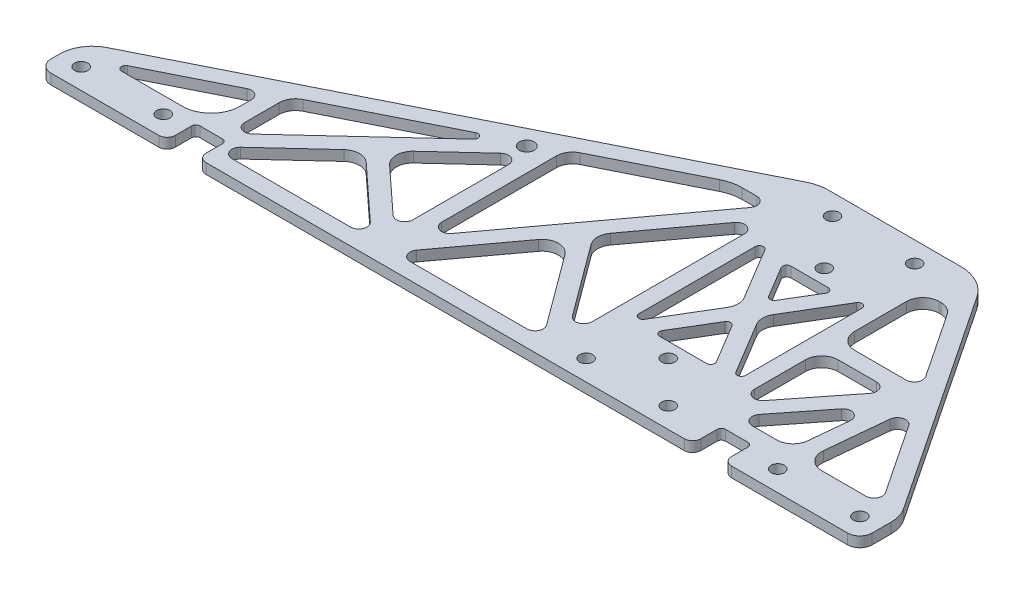
SolidWorks part; units mm, degrees
ref_plane "Front Plane" through (0, 0, 0) normal (0, 0, 1) x (1, 0, 0)
ref_plane "Top Plane" through (0, 0, 0) normal (0, 1, 0) x (1, 0, 0)
ref_plane "Right Plane" through (0, 0, 0) normal (1, 0, 0) x (0, 0, -1)
sketch "Sketch1" plane through (0, 0, 0) normal (0, 1, 0) x (1, 0, 0)
  line L0 (0, 0) -> (254, 0)
  line L2 (203.2, 88.9) -> (152.4, 88.9)
  line L4 (0, 0) -> (0, 12.7)
  line L5 (0, 12.7) -> (152.4, 88.9)
  line L6 (203.2, 88.9) -> (254, 12.7)
  line L7 (254, 12.7) -> (254, 0)
  line L8 (0, 6.35) -> (44.45, 6.35) construction
  line L9 (254, 6.35) -> (222.25, 6.35) construction
  line L10 (139.7, 82.55) -> (207.4333, 82.55) construction
  line L11 (44.45, 0) -> (44.45, 34.925) construction
  line L12 (156.6333, 12.7) -> (154.0933, 7.62)
  line L13 (224.7006, 47.4909) -> (221.314, 12.7) construction
  line L20 (127, 76.2) -> (211.6667, 76.2)
  line L21 (154.0933, 76.2) -> (101.6, 5.08) construction
  line L22 (154.0933, 12.7) -> (154.0933, 7.62)
  line L23 (247.8946, 12.7) -> (194.7333, 12.7)
  line L24 (224.7006, 47.4909) -> (197.2733, 12.7) construction
  line L28 (224.7006, 47.4909) -> (194.7333, 47.4909) construction
  line L31 (5.08, 9.5604) -> (153.5992, 83.82)
  line L32 (200.4813, 83.82) -> (153.5992, 83.82)
  line L33 (200.4813, 83.82) -> (248.92, 11.1619)
  line L34 (248.92, 11.1619) -> (248.92, 5.08)
  line L35 (5.08, 5.08) -> (248.92, 5.08)
  line L36 (5.08, 5.08) -> (5.08, 9.5604)
  line L37 (101.6, 5.08) -> (101.6, 57.8204) construction
  line L39 (127.8467, 40.64) -> (154.0933, 5.08) construction
  line L40 (101.6, 57.8204) -> (44.45, 5.08) construction
  line L41 (73.025, 31.4502) -> (101.6, 5.08) construction
  line L42 (154.0933, 7.62) -> (154.0933, 5.08)
  line L83 (152.8233, 5.08) -> (150.2833, 0)
  line L84 (125.803, 39.1316) -> (152.0497, 3.5716)
  line L107 (152.0497, 77.7084) -> (99.5564, 6.5884)
  line L108 (156.6333, 76.2) -> (194.7333, 12.7) construction
  line L113 (194.7333, 76.2) -> (156.6333, 12.7) construction
  line L117 (104.14, 5.08) -> (104.14, 63.6207)
  line L118 (156.6333, 12.7) -> (194.7333, 12.7)
  line L119 (194.7333, 12.7) -> (201.0833, 0)
  line L120 (154.0933, 6.35) -> (197.9083, 6.35) construction
  line L126 (192.5553, 77.5068) -> (154.4553, 14.0068)
  line L127 (154.4553, 74.8932) -> (192.5553, 11.3932)
  line L128 (156.6333, 12.7) -> (156.6333, 76.2) construction
  line L129 (194.7333, 12.7) -> (194.7333, 76.2) construction
  line L130 (197.2733, 12.7) -> (197.2733, 76.2)
  line L131 (159.1733, 12.7) -> (159.1733, 76.2)
  line L132 (192.1933, 12.7) -> (192.1933, 76.2)
  line L133 (154.0933, 12.7) -> (154.0933, 76.2)
  line L147 (196.9114, 74.8932) -> (158.8114, 11.3932)
  line L148 (158.8114, 77.5068) -> (196.9114, 14.0068)
  line L154 (104.14, 63.6207) -> (42.7274, 6.9466)
  line L155 (71.3024, 29.5836) -> (99.8774, 3.2134)
  line L156 (224.7006, 50.0309) -> (194.7333, 50.0309)
  line L157 (222.7059, 49.0635) -> (195.2786, 14.2725)
  line L158 (197.2733, 12.7) -> (197.2733, 7.62)
  line L159 (222.1726, 47.737) -> (218.7859, 12.9461)
  line L160 (129.8903, 42.1484) -> (156.137, 6.5884)
  line L163 (156.137, 74.6916) -> (103.6436, 3.5716)
  line L164 (99.06, 5.08) -> (99.06, 52.0201)
  line L165 (99.06, 52.0201) -> (46.1726, 3.2134)
  line L166 (175.6833, 19.05) -> (162.9833, 6.35) construction
  line L167 (175.6833, 19.05) -> (188.3833, 6.35) construction
  line L168 (162.9833, 82.55) -> (175.6833, 67.31) construction
  line L169 (175.6833, 67.31) -> (188.3833, 82.55) construction
  line L170 (161.6625, 21.082) -> (189.7041, 21.082) construction
  line L171 (161.6625, 23.622) -> (189.7041, 23.622)
  line L172 (163.1865, 65.278) -> (188.1801, 65.278) construction
  line L173 (163.1865, 62.738) -> (188.1801, 62.738)
  line L174 (74.7476, 33.3168) -> (103.3226, 6.9466)
  line L175 (224.7006, 44.9509) -> (194.7333, 44.9509)
  line L176 (226.6953, 45.9184) -> (199.268, 11.1275)
  line L177 (227.2287, 47.2449) -> (223.842, 12.4539)
  line L178 (8.8192, 11.43) -> (44.45, 11.43)
  line L179 (46.99, 0) -> (46.99, 34.925)
  line L180 (41.91, 0) -> (41.91, 34.925)
  line L181 (198.2745, 13.97) -> (221.4376, 13.97)
  circle A0 centre (6.7733, 6.35) radius 2.032
  circle A1 centre (32.1733, 6.35) radius 2.032
  circle A2 centre (222.25, 6.35) radius 2.032
  circle A3 centre (247.65, 6.35) radius 2.032
  circle A4 centre (162.9833, 82.55) radius 2.032
  circle A5 centre (188.3833, 82.55) radius 2.032
  circle A28 centre (162.9833, 6.35) radius 2.032
  circle A29 centre (188.3833, 6.35) radius 2.032
  arc A32 (197.2733, 12.7) -> (192.1933, 12.7) centre (194.7333, 12.7) cw
  arc A33 (197.2733, 76.2) -> (192.1933, 76.2) centre (194.7333, 76.2) ccw
  arc A34 (159.1733, 12.7) -> (154.0933, 12.7) centre (156.6333, 12.7) cw
  arc A35 (159.1733, 76.2) -> (154.0933, 76.2) centre (156.6333, 76.2) ccw
  arc A45 (192.5553, 77.5068) -> (196.9114, 74.8932) centre (194.7333, 76.2) cw
  arc A46 (154.4553, 14.0068) -> (158.8114, 11.3932) centre (156.6333, 12.7) ccw
  arc A47 (154.4553, 74.8932) -> (158.8114, 77.5068) centre (156.6333, 76.2) cw
  arc A48 (192.5553, 11.3932) -> (196.9114, 14.0068) centre (194.7333, 12.7) ccw
  circle A59 centre (175.6833, 19.05) radius 2.032
  circle A60 centre (175.6833, 67.31) radius 2.032
  arc A61 (125.803, 39.1316) -> (129.8903, 42.1484) centre (127.8467, 40.64) cw
  arc A62 (152.0497, 3.5716) -> (156.137, 6.5884) centre (154.0933, 5.08) ccw
  arc A63 (152.0497, 77.7084) -> (156.137, 74.6916) centre (154.0933, 76.2) cw
  arc A64 (99.5564, 6.5884) -> (103.6436, 3.5716) centre (101.6, 5.08) ccw
  arc A65 (104.14, 5.08) -> (99.06, 5.08) centre (101.6, 5.08) cw
  arc A66 (42.7274, 6.9466) -> (46.1726, 3.2134) centre (44.45, 5.08) ccw
  arc A67 (71.3024, 29.5836) -> (74.7476, 33.3168) centre (73.025, 31.4502) cw
  arc A68 (99.8774, 3.2134) -> (103.3226, 6.9466) centre (101.6, 5.08) ccw
  arc A69 (224.7006, 50.0309) -> (224.7006, 44.9509) centre (224.7006, 47.4909) cw
  arc A70 (194.7333, 50.0309) -> (194.7333, 44.9509) centre (194.7333, 47.4909) ccw
  arc A71 (222.7059, 49.0635) -> (226.6953, 45.9184) centre (224.7006, 47.4909) cw
  arc A72 (195.2786, 14.2725) -> (199.268, 11.1275) centre (197.2733, 12.7) ccw
  arc A73 (222.1726, 47.737) -> (227.2287, 47.2449) centre (224.7006, 47.4909) cw
  arc A74 (218.7859, 12.9461) -> (223.842, 12.4539) centre (221.314, 12.7) ccw
  arc A75 (46.99, 0) -> (41.91, 0) centre (44.45, 0) cw
  arc A76 (46.99, 34.925) -> (41.91, 34.925) centre (44.45, 34.925) ccw
  dimension "D7" = 4.064
  dimension "D8" = 25.4
  dimension "D9" = 130.81
  dimension "D10" = 25.4
  dimension "D11" = 6.35
  dimension "D13" = 19.05
  dimension "D1" = 254
  dimension "D2" = 50.8
  dimension "D3" = 88.9
  dimension "D4" = 152.4
  dimension "D5" = 12.7
  dimension "D6" = 6.35
  dimension "D12" = 25.4
  dimension "D14" = 44.45
  dimension "D15" = 12.7
  dimension "D16" = 57.15
  dimension "D18" = 12.7
  dimension "D19" = 2.54
  dimension "D20" = 50.8
  dimension "D21" = 25.4
  dimension "D22" = 2.54
  dimension "D23" = 6.35
  dimension "D24" = 2.54
  dimension "D29" = 6.35
  dimension "D30" = 38.1
  dimension "D31" = 25.4
  dimension "D32" = 6.35
  dimension "D33" = 2.54
  dimension "D36" = 12.7
  dimension "D38" = 15.24
  dimension "D39" = 2.54
  dimension "D40" = 2.54
  dimension "D27" = 1.27
  dimension "D17" = 5.08
  dimension "D25" = 2.54
  dimension "D26" = 2.54
  dimension "D37" = 2.54
extrude "Boss-Extrude1" add sketch "Sketch1" along normal blind 3.175 contours L0 L7 L6 L2 L5 L4 | A0 | A1 | A5 | A4 | A2 | A3
extrude "Cut-Extrude2" cut sketch "Sketch1<3>" along normal through all contours L154 L31 L11 | L155 L165 L35 | L165 L174 L164 | L117 L107 L20 L31 | L84 L163 L35 | L133 L163 L160 L22 | L157 L175 L130 | L156 L33 L20 L130 | L147 L148 L132 | L131 L126 L127 | L173 L148 L126 | L147 L171 L127 | L33 L177 L23 | L178 L180 L31 | L176 L181 L159 | A28 | A59 | A29 | A60 region at (30.8797, 0, -16.9451) region at (73.025, 0, -12.718) region at (62.4687, 0, -31.7097) region at (120.7695, 0, -51.2726) region at (127.8467, 0, -15.5076) region at (91.6301, 0, -31.4502) region at (206.5243, 0, -60.8789) region at (146.3968, 0, -40.64) region at (204.6702, 0, -35.5682) region at (175.6833, 0, -28.919) region at (187.6774, 0, -44.45) region at (213.9093, 0, -22.3524) region at (163.6893, 0, -44.45) region at (232.896, 0, -23.1836) region at (175.6833, 0, -58.2876)
sketch "Sketch1<3>" plane through (0, 0, 0) normal (0, 1, 0) x (1, 0, 0) same geometry as "Sketch1"
fillet "Fillet1" radius 3.81 2 edges at (254, 1.5875, 0) (0, 1.5875, 0)
fillet "Fillet2" radius 10.16 2 edges at (254, 1.5875, -12.7) (0, 1.5875, -12.7)
fillet "Fillet3" radius 12.7 2 edges at (203.2, 1.5875, -88.9) (152.4, 1.5875, -88.9)
fillet "Fillet4" radius 1.27 12 edges at (159.1733, 1.5875, -67.0298) (192.1933, 1.5875, -67.0298) (192.1933, 1.5875, -21.8702) (159.1733, 1.5875, -21.8702) (183.694, 1.5875, -62.738) (167.6727, 1.5875, -62.738) (175.6833, 1.5875, -49.3869) (185.218, 1.5875, -23.622) (166.1487, 1.5875, -23.622) (175.6833, 1.5875, -39.5131) (93.426, 1.5875, -53.7334) (8.8192, 1.5875, -11.43)
fillet "Fillet5" radius 2.54 19 edges at (223.0073, 1.5875, -50.0309) (247.8946, 1.5875, -12.7) (226.9275, 1.5875, -44.1507) (221.3335, 1.5875, -39.1171) (197.2733, 1.5875, -16.8027) (219.4639, 1.5875, -44.9509) (104.14, 1.5875, -12.7984) (99.06, 1.5875, -52.0201) (48.1953, 1.5875, -5.08) (97.8547, 1.5875, -5.08) (99.06, 1.5875, -10.8803) (104.7569, 1.5875, -5.08) (150.9364, 1.5875, -5.08) (154.0933, 1.5875, -9.3572) (154.0933, 1.5875, -71.9228) (150.9364, 1.5875, -76.2) (41.91, 1.5875, -27.9754) (46.99, 1.5875, -10.8803) (201.5089, 1.5875, -13.97)
fillet "Fillet6" radius 5.08 14 edges at (172.7212, 1.5875, -44.45) (178.6455, 1.5875, -44.45) (223.866, 1.5875, -12.7) (197.2733, 1.5875, -50.0309) (197.2733, 1.5875, -44.9509) (197.2733, 1.5875, -76.2) (205.5613, 1.5875, -76.2) (73.025, 1.5875, -27.9939) (76.7703, 1.5875, -31.4502) (104.14, 1.5875, -59.0904) (131.0036, 1.5875, -40.64) (127.8467, 1.5875, -36.3628) (46.99, 1.5875, -30.5154) (218.8856, 1.5875, -13.97)
fillet "Fillet7" radius 12.7 1 edges at (138.3592, 1.5875, -76.2)
fillet "Fillet10" radius 8.89 1 edges at (41.91, 1.5875, -11.43)
sketch "Sketch2" plane through (0, 3.175, 0) normal (0, 1, 0) x (1, 0, 0)
  line L0 (39.6875, 0) -> (39.6875, 8.89)
  line L1 (3.81, 0) -> (250.19, 0) construction
  line L2 (39.6875, 8.89) -> (49.2125, 8.89)
  line L3 (49.2125, 8.89) -> (49.2125, 0)
  line L4 (0, 3.81) -> (0, 6.4208) construction
  line L5 (202.2475, 0) -> (202.2475, 8.89)
  line L6 (202.2475, 8.89) -> (211.7725, 8.89)
  line L7 (211.7725, 8.89) -> (211.7725, 0)
  line L8 (254, 9.6238) -> (254, 3.81) construction
  line L9 (3.81, 0) -> (250.19, 0)
  dimension "D1" = 39.6875
  dimension "D2" = 9.525
  dimension "D3" = 8.89
  dimension "D4" = 42.2275
extrude "Cut-Extrude3" cut sketch "Sketch2" against normal through all contours L0 L9 L3 L2 | L5 L9 L7 L6 region at (207.01, 3.175, -4.445) region at (44.45, 3.175, -4.445)
fillet "Fillet8" radius 1.27 4 edges at (211.7725, 1.5875, -8.89) (202.2475, 1.5875, -8.89) (49.2125, 1.5875, -8.89) (39.6875, 1.5875, -8.89)
fillet "Fillet9" radius 2.54 4 edges at (49.2125, 1.5875, 0) (39.6875, 1.5875, 0) (211.7725, 1.5875, 0) (202.2475, 1.5875, 0)
sketch "Sketch3" plane through (0, 3.175, 0) normal (0, 1, 0) x (1, 0, 0)
  line L0 (256.4001, 55.614) -> (97.371, 67.7718) construction
  circle A0 centre (256.4001, 55.614) radius 2.286 construction
  circle A1 centre (256.4001, 55.614) radius 2.286
  circle A2 centre (96.9147, 54.0396) radius 2.286
  arc A4 (97.371, 67.7718) -> (103.7118, 9.5233) centre (256.4001, 55.614) ccw construction
  point P5 (95.431, 54.0258)
  dimension "D1" = 159.4931
  dimension "D2" = 4.572
extrude "Cut-Extrude4" cut sketch "Sketch3" against normal up to surface (3.175 mm away) contours A2 region at (96.9147, 3.175, -54.0396) up to face at (233.1564, 0, -22.5815)
